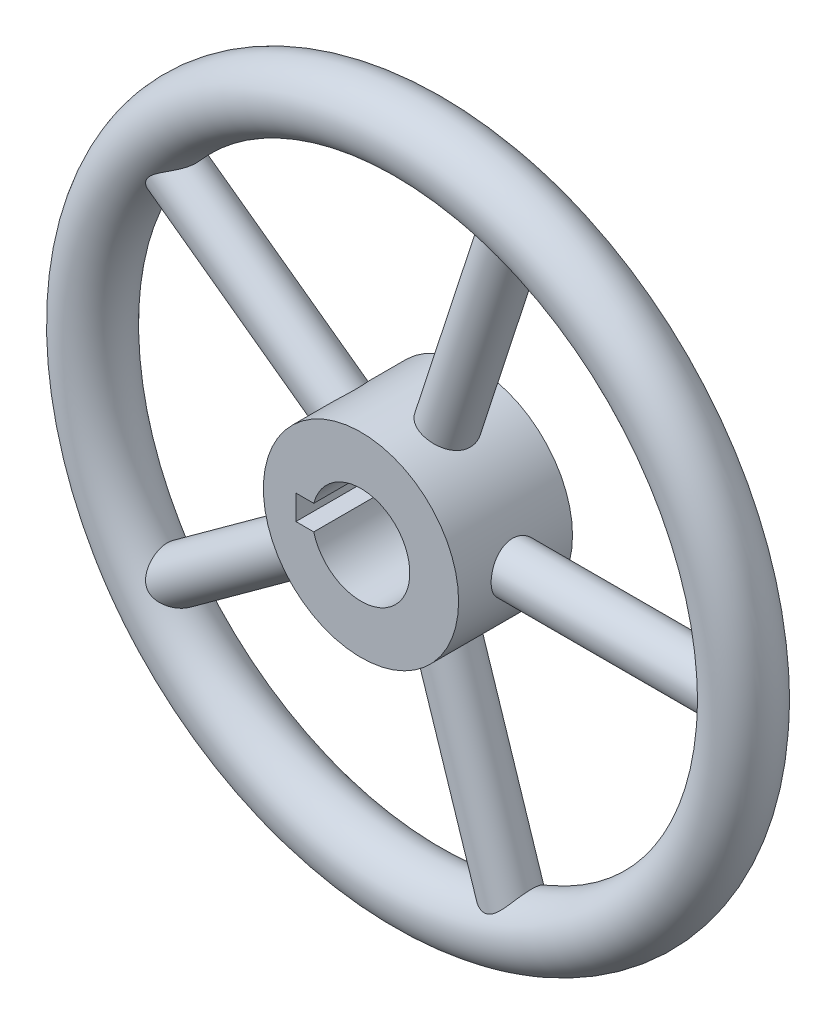
SolidWorks part; units mm, degrees
ref_plane "Alzado" through (0, 0, 0) normal (0, 0, 1) x (1, 0, 0)
ref_plane "Planta" through (0, 0, 0) normal (0, 1, 0) x (1, 0, 0)
ref_plane "Vista lateral" through (0, 0, 0) normal (1, 0, 0) x (0, 0, -1)
sketch "Croquis2" plane through (0, 0, 0) normal (0, 0, 1) x (1, 0, 0)
  circle A0 centre (0, 0) radius 38.1
  dimension "D1" = 76.2
extrude "Saliente-Extruir1" add sketch "Croquis2" along normal blind 44.45
sketch "Croquis4" plane through (0, 0, 0) normal (1, 0, 0) x (0, 0, -1)
  line L0 (-44.45, 0) -> (0, 0) construction
  line L1 (-44.45, 38.1) -> (-44.45, -38.1) construction
  circle A0 centre (-22.225, 0) radius 9.525
  dimension "D1" = 19.05
extrude "Saliente-Extruir3" add sketch "Croquis4" along normal blind 127
ref_axis "Eje3" through (0, 0, 44.45) along (0, 0, -1)
pattern_circular "MatrizC2" count 5 over 360 about axis through (0, 0, 44.45) along (0, 0, -1) of "Saliente-Extruir3"
ref_plane "Plano2" through (0, 0, 22.225) normal (0, 0, 1) x (1, 0, 0)
sketch "Croquis8" plane through (0, 0, 0) normal (1, 0, 0) x (0, 0, -1)
  circle A0 centre (-22.225, 127) radius 12.7
  dimension "D1" = 25.4
  dimension "D2" = 127
revolve "Revolución1" add sketch "Croquis8" angle 360 about axis through (0, 0, 44.45) along (0, 0, -1)
sketch "Croquis9" plane through (0, 0, 44.45) normal (0, 0, 1) x (1, 0, 0)
  line L0 (0, 0) -> (-38.1, 0) construction
  line L1 (-18.4286, 4.826) -> (-25.4, 4.826)
  line L2 (-25.4, 4.826) -> (-25.4, -4.826)
  line L3 (-25.4, -4.826) -> (-18.4286, -4.826)
  arc A0 (-18.4286, -4.826) -> (-18.4286, 4.826) centre (0, 0) ccw
  circle A1 centre (0, 0) radius 38.1 construction
  dimension "D1" = 38.1
  dimension "D2" = 25.4
  dimension "D3" = 9.652
  dimension "D4" = 4.826
extrude "Cortar-Extruir1" cut sketch "Croquis9" against normal through all
